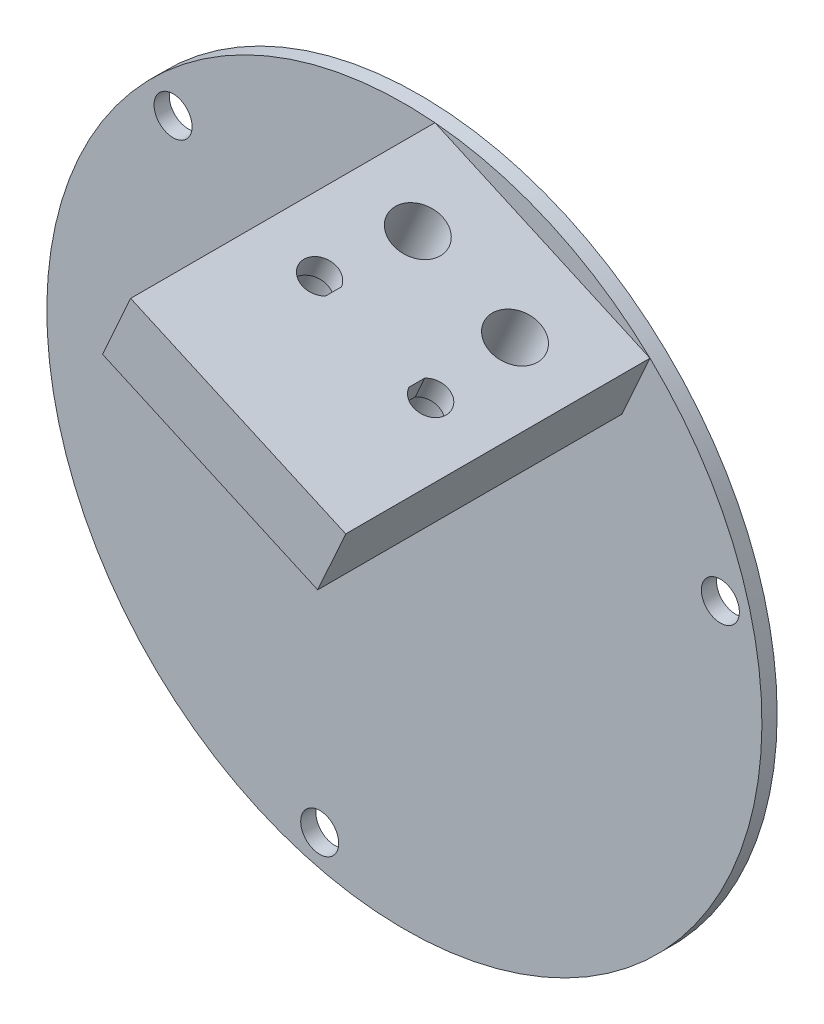
SolidWorks part; units mm, degrees
ref_plane "Plan de face" through (0, 0, 0) normal (0, 0, 1) x (1, 0, 0)
ref_plane "Plan de dessus" through (0, 0, 0) normal (0, 1, 0) x (1, 0, 0)
ref_plane "Plan de droite" through (0, 0, 0) normal (1, 0, 0) x (0, 0, -1)
sketch "Sketch1" plane through (0, 0, 0) normal (0, 0, 1) x (1, 0, 0)
  circle A0 centre (0, 0) radius 47
  dimension "D1" = 94
extrude "Boss-Extrude1" add sketch "Sketch1" along normal blind 2
sketch "Sketch3" plane through (0, 0, 0) normal (0, 0, -1) x (-1, 0, 0)
  line L0 (0, 0) -> (0, 43) construction
  line L1 (0, 0) -> (30.4056, 30.4056) construction
  circle A0 centre (0, 0) radius 43 construction
  circle A1 centre (30.4056, 30.4056) radius 2.5
  circle A2 centre (11.1292, -41.5348) radius 2.5
  circle A3 centre (-41.5348, 11.1292) radius 2.5
  point P13 (0, 0)
  dimension "D1" = 86
  dimension "D2" = 5
  dimension "D3" = 45
  dimension "D4" = 3
extrude "Cut-Extrude1" cut sketch "Sketch3" against normal through all contours A3 | A1 | A2
sketch "Sketch4" plane through (0, 0, 2) normal (0, 0, 1) x (1, 0, 0)
  line L0 (-22.2135, -49.5439) -> (25.9538, 57.8861) construction
  line L3 (-30.4056, 30.4056) -> (42.9287, -2.4745) construction
  line L6 (4.021, 46.8277) -> (32.2879, 34.1539)
  line L7 (32.2879, 34.1539) -> (28.6058, 25.9416)
  line L8 (28.6058, 25.9416) -> (0.3389, 38.6154)
  line L9 (0.3389, 38.6154) -> (4.021, 46.8277)
  circle A2 centre (-30.4056, 30.4056) radius 2.5 construction
  circle A3 centre (0, 0) radius 47 construction
  circle A6 centre (-30.4056, 30.4056) radius 2.5 construction
  circle A7 centre (0, 0) radius 47 construction
  circle A8 centre (-30.4056, 30.4056) radius 4.25 construction
  circle A9 centre (42.9287, -2.4745) radius 2.5 construction
  circle A10 centre (42.9287, -2.4745) radius 4.25 construction
  circle A11 centre (-22.2135, -49.5439) radius 2.5 construction
  circle A12 centre (-22.2135, -49.5439) radius 4.25 construction
  point P0 (0, 0)
  point P16 (-3.2301, -7.2043)
  point P18 (14.444, 32.2151)
  point P19 (18.1544, 40.4908)
  dimension "D1" = 8.5
  dimension "D3" = 9
  dimension "D2" = 3
extrude "Boss-Extrude2" add sketch "Sketch4" along normal blind 40
sketch "Sketch8" plane through (18.1544, 40.4908, 0) normal (0.4091, 0.9125, 0) x (0.9125, -0.4091, 0)
  line L0 (0, -2) -> (0, -42) construction
  line L3 (15.489, -2) -> (-15.489, -2) construction
  line L4 (15.489, -42) -> (-15.489, -42) construction
  line L5 (-7, -12) -> (7, -12) construction
  line L6 (0, -24) -> (8, -24) construction
  line L7 (6, -22.9692) -> (6, -25.0308)
  line L8 (-6, -22.9692) -> (-6, -25.0308)
  circle A0 centre (7, -12) radius 3.25
  arc A1 (6, -22.9692) -> (6, -25.0308) centre (8, -24) cw
  arc A2 (-6, -22.9692) -> (-6, -25.0308) centre (-8, -24) ccw
  circle A3 centre (-7, -12) radius 3.25
  point P9 (0, -12)
  point P12 (0, -24)
  point P16 (6, -24)
  dimension "D3" = 6.5
  dimension "D5" = 2.25
  dimension "D1" = 7
  dimension "D2" = 8
  dimension "D4" = 2
  dimension "D6" = 12
  dimension "D7" = 10
extrude "Cut-Extrude3" cut sketch "Sketch8" against normal up to next
sketch "Sketch9" plane through (14.4724, 32.2785, 0) normal (-0.4091, -0.9125, 0) x (0.9125, -0.4091, 0)
  line L0 (0, 2) -> (0, 42) construction
  line L1 (47, 2) -> (-47, 2) construction
  line L2 (-15.489, 42) -> (15.489, 42) construction
  line L3 (-1.5, 18.5) -> (-12.5, 18.5)
  line L4 (1.5, 5.5) -> (12.5, 5.5)
  line L5 (1.5, 5.5) -> (1.5, 18.5)
  line L6 (1.5, 18.5) -> (12.5, 18.5)
  line L7 (12.5, 5.5) -> (12.5, 18.5)
  line L8 (1.5, 5.5) -> (12.5, 18.5) construction
  line L9 (1.5, 18.5) -> (12.5, 5.5) construction
  line L10 (-12.5, 5.5) -> (-12.5, 18.5)
  line L11 (-1.5, 5.5) -> (-12.5, 5.5)
  line L12 (-1.5, 5.5) -> (-1.5, 18.5)
  arc A0 (6, 22.9692) -> (6, 25.0308) centre (8, 24) ccw construction
  circle A1 centre (7, 12) radius 3.25 construction
  arc A2 (6, 22.9692) -> (6, 25.0308) centre (8, 24) ccw construction
  circle A3 centre (7, 12) radius 3.25 construction
  dimension "D1" = 13
  dimension "D2" = 11
extrude "Cut-Extrude4" cut sketch "Sketch9" against normal blind 1
sketch "Sketch10" plane through (14.4724, 32.2785, 0) normal (-0.4091, -0.9125, 0) x (0.9125, -0.4091, 0)
  line L0 (0, 2) -> (0, 42) construction
  line L1 (-15.489, 2) -> (15.489, 2) construction
  line L2 (-15.489, 42) -> (15.489, 42) construction
  arc A0 (6, 22.9692) -> (6, 25.0308) centre (8, 24) ccw construction
  arc A1 (6, 22.9692) -> (6, 25.0308) centre (8, 24) ccw construction
  circle A2 centre (8, 24) radius 3.125
  circle A3 centre (-8, 24) radius 3.125
  dimension "D1" = 6.25
extrude "Cut-Extrude5" cut sketch "Sketch10" against normal blind 6
